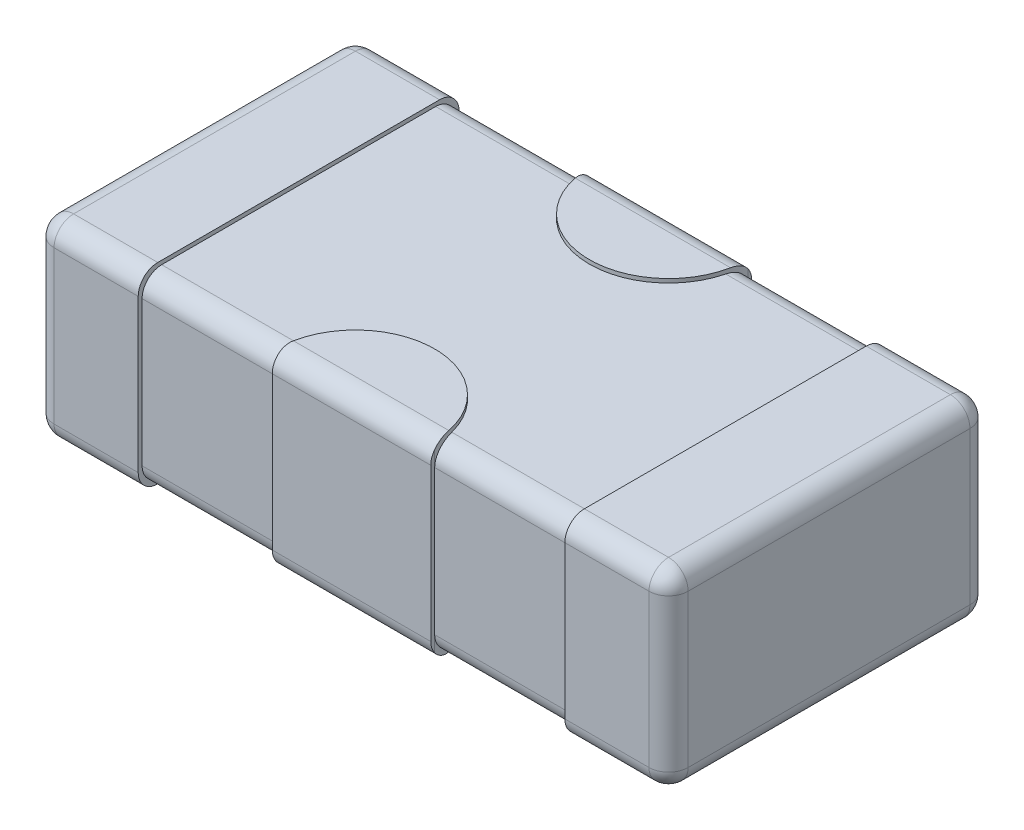
SolidWorks part; units mm, degrees
ref_plane "Front Plane" through (0, 0, 0) normal (0, 0, 1) x (1, 0, 0)
ref_plane "Top Plane" through (0, 0, 0) normal (0, 1, 0) x (1, 0, 0)
ref_plane "Right Plane" through (0, 0, 0) normal (1, 0, 0) x (0, 0, -1)
sketch "Sketch1" plane through (0, 0, 0) normal (0, 1, 0) x (1, 0, 0)
  line L1 (-1.6, 0.8) -> (1.6, 0.8)
  line L2 (-1.6, 0.8) -> (-1.6, -0.8)
  line L3 (-1.6, -0.8) -> (1.6, -0.8)
  line L4 (1.6, 0.8) -> (1.6, -0.8)
  line L5 (-1.6, 0.8) -> (1.6, -0.8) construction
  line L6 (-1.6, -0.8) -> (1.6, 0.8) construction
  point P0 (0, 0)
  dimension "D1" = 3.2
  dimension "D2" = 1.6
extrude "Boss-Extrude1" add sketch "Sketch1" along normal blind 0.94
sketch "Sketch2" plane through (0, 0.94, 0) normal (0, 1, 0) x (1, 0, 0)
  line L0 (-0.405, 0.82) -> (-0.405, 0.8)
  line L1 (-1.62, 0.82) -> (-1.09, 0.82)
  line L2 (-1.62, 0.82) -> (-1.62, -0.82)
  line L3 (-1.62, -0.82) -> (-1.09, -0.82)
  line L4 (-1.09, 0.82) -> (-1.09, -0.82)
  line L5 (1.6, 0.8) -> (-1.6, 0.8) construction
  line L7 (0, 0) -> (0, 0.8) construction
  line L9 (0.405, 0.82) -> (0.405, 0.8)
  line L10 (-0.405, 0.82) -> (0.405, 0.82)
  line L11 (0, 0) -> (-2.1159, 0) construction
  line L12 (-1.6, 0.8) -> (-1.6, -0.8) construction
  line L13 (1.62, -0.82) -> (1.09, -0.82)
  line L14 (1.09, 0.82) -> (1.09, -0.82)
  line L15 (1.62, 0.82) -> (1.09, 0.82)
  line L16 (1.62, 0.82) -> (1.62, -0.82)
  line L17 (-0.405, -0.82) -> (-0.405, -0.8)
  line L18 (0.405, -0.82) -> (0.405, -0.8)
  line L19 (-0.405, -0.82) -> (0.405, -0.82)
  arc A0 (-0.405, 0.8) -> (0.405, 0.8) centre (0, 0.8) ccw
  arc A1 (-0.405, -0.8) -> (0.405, -0.8) centre (0, -0.8) cw
  point P16 (0, 0)
  dimension "D1" = 0.81
  dimension "D2" = 0.02
  dimension "D3" = 0.02
  dimension "D4" = 0.51
extrude "Boss-Extrude2" add sketch "Sketch2" along normal blind 0.02
sketch "Sketch3" plane through (0, 0.94, 0) normal (0, 1, 0) x (1, 0, 0)
  line L3 (-0.405, 0.82) -> (-0.405, 0.8)
  line L4 (-1.09, 0.82) -> (-1.62, 0.82)
  line L5 (-1.09, -0.82) -> (-1.09, 0.82)
  line L6 (-1.62, -0.82) -> (-1.09, -0.82)
  line L7 (-1.62, 0.82) -> (-1.62, -0.82)
  line L8 (-1.09, 0.82) -> (-1.62, 0.82)
  line L9 (-1.09, -0.82) -> (-1.09, 0.82)
  line L10 (-1.62, -0.82) -> (-1.09, -0.82)
  line L11 (-1.62, 0.82) -> (-1.62, -0.82)
  line L12 (0.405, 0.8) -> (0.405, 0.82)
  line L13 (0.405, 0.82) -> (-0.405, 0.82)
  line L14 (-0.405, 0.82) -> (-0.405, 0.8)
  line L15 (0.405, 0.8) -> (0.405, 0.82)
  line L16 (0.405, 0.82) -> (-0.405, 0.82)
  line L17 (-0.405, -0.8) -> (-0.405, -0.82)
  line L18 (0.405, -0.82) -> (0.405, -0.8)
  line L19 (-0.405, -0.82) -> (0.405, -0.82)
  line L20 (-0.405, -0.8) -> (-0.405, -0.82)
  line L21 (0.405, -0.82) -> (0.405, -0.8)
  line L22 (-0.405, -0.82) -> (0.405, -0.82)
  line L24 (1.09, -0.82) -> (1.62, -0.82)
  line L25 (1.09, 0.82) -> (1.09, -0.82)
  line L26 (1.62, 0.82) -> (1.09, 0.82)
  line L27 (1.62, -0.82) -> (1.62, 0.82)
  line L28 (1.09, -0.82) -> (1.62, -0.82)
  line L29 (1.09, 0.82) -> (1.09, -0.82)
  line L30 (1.62, 0.82) -> (1.09, 0.82)
  line L31 (1.62, -0.82) -> (1.62, 0.82)
  arc A1 (-0.405, 0.8) -> (0.405, 0.8) centre (0, 0.8) ccw
  arc A2 (-0.405, 0.8) -> (0.405, 0.8) centre (0, 0.8) ccw
  arc A3 (0.405, -0.8) -> (-0.405, -0.8) centre (0, -0.8) ccw
  arc A4 (0.405, -0.8) -> (-0.405, -0.8) centre (0, -0.8) ccw
  dimension "D1" = 0
  dimension "D2" = 0
  dimension "D3" = 0
  dimension "D4" = 0
extrude "Boss-Extrude3" add sketch "Sketch3" against normal blind 0.96
fillet "Fillet1" radius 0.1 24 edges at (1.62, 0.96, 0) (1.62, 0.47, -0.82) (1.62, -0.02, 0) (1.62, 0.47, 0.82) (-1.62, 0.96, 0) (-1.62, 0.47, 0.82) (-1.62, -0.02, 0) (-1.62, 0.47, -0.82) (1.355, -0.02, 0.82) (1.355, 0.96, 0.82) (1.355, 0.96, -0.82) (1.355, -0.02, -0.82) (-1.355, -0.02, -0.82) (-1.355, 0.96, -0.82) (-1.355, -0.02, 0.82) (-1.355, 0.96, 0.82) (-0.7475, 0, -0.8) (0.7475, 0, -0.8) (0.7475, 0.94, -0.8) (-0.7475, 0.94, -0.8) (-0.7475, 0, 0.8) (0.7475, 0, 0.8) (0.7475, 0.94, 0.8) (-0.7475, 0.94, 0.8)
fillet "Fillet2" radius 0.1 4 edges at (0, -0.02, -0.82) (0, -0.02, 0.82) (0, 0.96, -0.82) (0, 0.96, 0.82)
